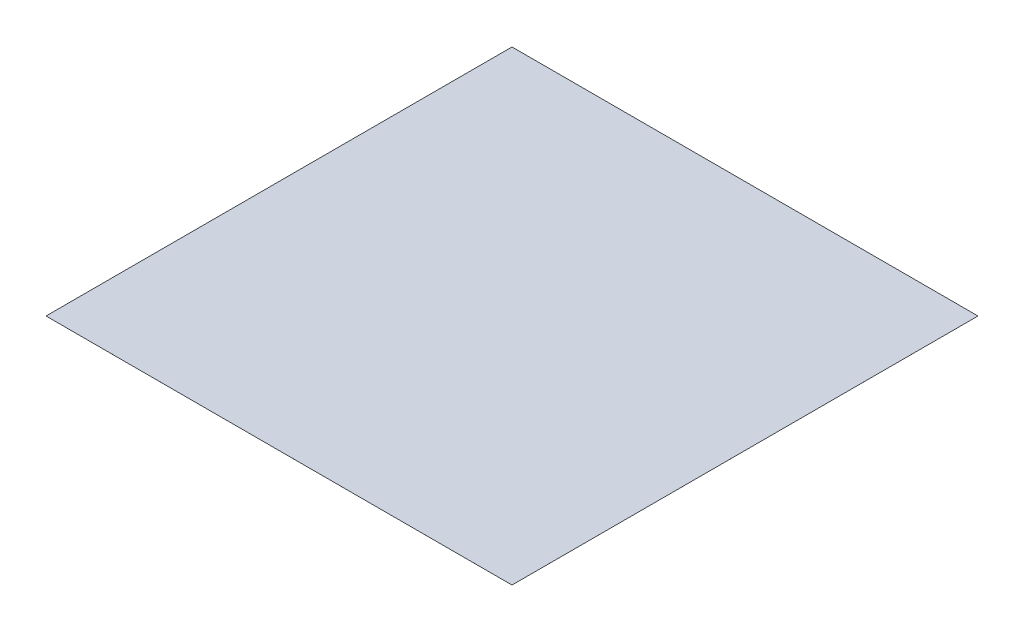
SolidWorks part; units mm, degrees
ref_plane "Plan de face" through (0, 0, 0) normal (0, 0, 1) x (1, 0, 0)
ref_plane "Plan de dessus" through (0, 0, 0) normal (0, 1, 0) x (1, 0, 0)
ref_plane "Plan de droite" through (0, 0, 0) normal (1, 0, 0) x (0, 0, -1)
sketch "Esquisse1" plane through (0, 0, 0) normal (0, 0, 1) x (1, 0, 0)
  line L1 (-5000, -0.025) -> (5000, -0.025)
  line L2 (-5000, -0.025) -> (-5000, 0.025)
  line L3 (-5000, 0.025) -> (5000, 0.025)
  line L4 (5000, -0.025) -> (5000, 0.025)
  point P4 (0, 0)
  point P5 (0, -0.025)
  point P6 (5000, 0)
  dimension "D1" = 10000
  dimension "D2" = 0.05
  dimension "D3" = 0
  dimension "D4" = 0
extrude "Boss.-Extru.2" add sketch "Esquisse1" along normal blind 5000 and the other way blind 5000
